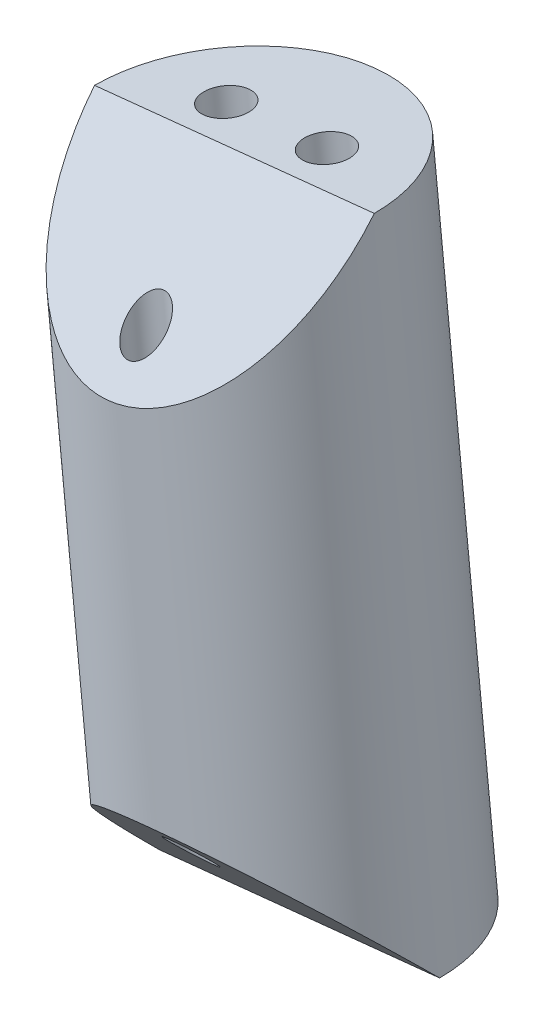
SolidWorks part; units mm, degrees
ref_plane "Front Plane" through (0, 0, 0) normal (0, 0, 1) x (1, 0, 0)
ref_plane "Top Plane" through (0, 0, 0) normal (0, 1, 0) x (1, 0, 0)
ref_plane "Right Plane" through (0, 0, 0) normal (1, 0, 0) x (0, 0, -1)
sketch "Sketch2" plane through (0, 0, 0) normal (0, 0, 1) x (1, 0, 0)
  line L0 (0, 0) -> (90, 0)
  line L1 (90, 0) -> (90, 120)
  line L2 (90, 120) -> (0, 120)
  line L3 (0, 120) -> (0, 0)
  line L4 (0, 120) -> (-10, 120)
  line L5 (-10, 120) -> (-10, 16.9491)
  line L6 (-10, 120) -> (57.5, 127)
  line L7 (57.5, 127) -> (90, 124)
  line L8 (90, 120) -> (99, 60)
  line L10 (90, 124) -> (90, 120)
  line L11 (5.9147, 0) -> (5.9147, -25)
  line L12 (5.9147, -25) -> (-4.0853, -25)
  line L13 (-4.0853, -29) -> (-4.0853, 0)
  line L14 (80, 0) -> (80, -25)
  line L15 (80, -25) -> (90, -25)
  line L16 (90, -29) -> (90, 0)
  line L17 (15.7927, 122.6748) -> (5.4776, 222.1414)
  line L18 (5.4776, 222.1414) -> (21.3923, 223.7918)
  line L19 (21.3923, 223.7918) -> (31.7073, 124.3252)
  line L20 (7.6492, 201.201) -> (23.5639, 202.8514)
  line L21 (10.9066, 169.7905) -> (26.8212, 171.441)
  line L22 (-10, 120) -> (-20.0396, 216.8108)
  line L23 (-20.0396, 216.8108) -> (-4.125, 218.4612)
  line L24 (-4.125, 218.4612) -> (5.9147, 121.6504)
  line L25 (-17.926, 196.4296) -> (-2.0114, 198.08)
  line L26 (-14.7556, 165.8578) -> (1.159, 167.5082)
  line L27 (57.5, 127) -> (46.9095, 229.1223)
  line L28 (46.9095, 229.1223) -> (30.9949, 227.4719)
  line L29 (30.9949, 227.4719) -> (41.5853, 125.3496)
  line L30 (33.2245, 205.9725) -> (49.1391, 207.6229)
  line L31 (36.5688, 173.7233) -> (52.4835, 175.3737)
  line L34 (90, 124) -> (99.1917, 223.5767)
  line L35 (99.1917, 223.5767) -> (83.2594, 225.0473)
  line L36 (83.2594, 225.0473) -> (74.0677, 125.4707)
  line L38 (81.3243, 204.0838) -> (97.2566, 202.6132)
  line L39 (78.4217, 172.6386) -> (94.354, 171.1679)
  line L40 (62.4078, 79.6749) -> (57.5, 127) construction
  line L41 (41.5853, 125.3496) -> (46.4931, 78.0244) construction
  line L42 (46.4931, 78.0244) -> (62.4078, 79.6749) construction
  line L43 (31.7073, 124.3252) -> (36.6151, 77.0001) construction
  line L44 (36.6151, 77.0001) -> (20.7005, 75.3496) construction
  line L45 (20.7005, 75.3496) -> (15.7927, 122.6748) construction
  line L46 (5.9147, 121.6504) -> (10.8224, 74.3253) construction
  line L47 (10.8224, 74.3253) -> (-5.0922, 72.6749) construction
  line L48 (-5.0922, 72.6749) -> (-10, 120) construction
  line L49 (74.0677, 125.4707) -> (69.6944, 78.0931) construction
  line L50 (69.6944, 78.0931) -> (85.7624, 78.0931) construction
  line L51 (85.7624, 78.0931) -> (90, 124) construction
  line L52 (-12.0823, 217.636) -> (10.4873, 0) construction
  line L53 (13.4349, 222.9666) -> (36.5574, 0) construction
  line L54 (38.9522, 228.2971) -> (62.6275, 0) construction
  line L55 (91.2256, 224.312) -> (70.5198, 0) construction
  line L59 (99, 60) -> (93.5277, 44.9649)
  line L60 (99, 60) -> (169.4769, 34.3485)
  line L61 (169.4769, 34.3485) -> (164.0046, 19.3134)
  line L62 (164.0046, 19.3134) -> (93.5277, 44.9649)
  line L63 (90, -2) -> (100, -2)
  line L64 (141.2862, 44.6091) -> (135.8138, 29.574)
  line L65 (99, 60) -> (55.7741, 75.7329) construction
  line L66 (55.7741, 75.7329) -> (50.3018, 60.6978) construction
  line L67 (100, -2) -> (100, -29)
  line L70 (-4.0853, -2) -> (-14.0853, -2)
  line L71 (-14.0853, -2) -> (-14.0853, -29)
  line L74 (-4.0853, 0) -> (0, 0)
  line L75 (-14.0853, -29) -> (-14.0853, -112.587)
  line L76 (-14.0853, -112.587) -> (100, -112.587)
  line L77 (100, -112.587) -> (100, -29)
  line L78 (-14.0853, -29) -> (100, -29)
  line L79 (-14.0853, -14.5) -> (100, -14.5) construction
  line L80 (31.7073, -112.587) -> (31.7073, -122.6232)
  line L81 (31.7073, -122.6232) -> (42.9573, -122.6232)
  line L82 (42.9573, -122.6232) -> (42.9573, -112.587)
  line L83 (-14.0853, -112.587) -> (-88.3667, -112.587)
  line L84 (-88.3667, -112.587) -> (-88.3667, -128.2699)
  line L85 (-88.3667, -128.2699) -> (169.4958, -128.2699)
  line L86 (169.4958, -128.2699) -> (169.4958, -112.587)
  line L87 (169.4958, -112.587) -> (100, -112.587)
  line L88 (90, 60) -> (-10, 60) construction
  line L89 (50.3018, 60.6978) -> (93.5277, 44.9649) construction
  line L90 (87.2806, 55.7521) -> (166.7408, 26.8309) construction
  line L91 (87.2806, 55.7521) -> (82.1749, 52.5336) construction
  line L92 (82.1749, 52.5336) -> (77.3257, 0) construction
  line L93 (83.1185, 56.6957) -> (86.337, 51.59) construction
  arc A0 (-10, 16.9491) -> (-4.0853, 0) centre (14.9876, 16.1624) ccw
  arc A1 (93.5277, 44.9649) -> (90, 0) centre (-126.4069, 39.5988) cw
  point P42 (41.1818, 206.7977)
  point P100 (84.7278, 54.1428)
  point P101 (84.7278, 54.1428)
  dimension "D11" = 47.3684
  dimension "D35" = 9
  dimension "D32" = 220
  dimension "D36" = 25
  dimension "D1" = 120
  dimension "D2" = 90
  dimension "D3" = 10
  dimension "D5" = 67.862
  dimension "D6" = 7
  dimension "D7" = 4
  dimension "D8" = 16
  dimension "D9" = 16
  dimension "D10" = 100
  dimension "D12" = 31.5789
  dimension "D13" = 16
  dimension "D14" = 16
  dimension "D15" = 16
  dimension "D16" = 25.7927
  dimension "D17" = 100
  dimension "D18" = 21.0526
  dimension "D19" = 31.5789
  dimension "D20" = 97.33
  dimension "D21" = 102.67
  dimension "D22" = 20.4905
  dimension "D23" = 30.7358
  dimension "D24" = 21.6147
  dimension "D25" = 32.4221
  dimension "D26" = 25
  dimension "D28" = 25
  dimension "D29" = 75
  dimension "D30" = 47.5789
  dimension "D31" = 30
  dimension "D33" = 46
  dimension "D34" = 20
  dimension "D37" = 2
  dimension "D38" = 2
  dimension "D39" = 27
  dimension "D40" = 10
  dimension "D41" = 10
  dimension "D42" = 27
  dimension "D43" = 14.5
  dimension "D44" = 127.5
ref_plane "Plane1" through (87.2806, 55.7521, 0) normal (-0.846, -0.5333, 0) x (0, 0, 1)
ref_plane "Plane2" through (82.1749, 52.5336, 0) normal (-0.0919, -0.9958, 0) x (-0.9958, 0.0919, 0)
ref_plane "Plane3" through (91.2256, 224.312, 0) normal (-0.0919, -0.9958, 0) x (-0.9958, 0.0919, 0)
ref_plane "Plane4" through (38.9522, 228.2971, 0) normal (0.1032, -0.9947, 0) x (-0.9947, -0.1032, 0)
ref_plane "Plane5" through (13.4349, 222.9666, 0) normal (0.1032, -0.9947, 0) x (-0.9947, -0.1032, 0)
ref_plane "Plane7" through (166.7408, 26.8309, 0) normal (0.9397, -0.342, 0) x (0, 0, -1)
ref_plane "Plane8" through (110.4217, -40.1902, 0) normal (0.9397, -0.342, 0) x (0, 0, -1)
ref_plane "Plane9" through (19.3664, 209.803, 0) normal (-0.0919, -0.9958, 0) x (-0.9958, 0.0919, 0)
ref_plane "Plane10" through (16.4638, 178.3578, 0) normal (-0.0919, -0.9958, 0) x (-0.9958, 0.0919, 0)
ref_plane "Plane11" through (-20.7793, 200.3721, 0) normal (0.1032, -0.9947, 0) x (-0.9947, -0.1032, 0)
ref_plane "Plane12" through (-17.435, 168.1229, 0) normal (0.1032, -0.9947, 0) x (-0.9947, -0.1032, 0)
ref_plane "Plane13" through (-20.5619, 198.2754, 0) normal (0.1032, -0.9947, 0) x (-0.9947, -0.1032, 0)
ref_plane "Plane14" through (-17.3045, 166.8649, 0) normal (0.1032, -0.9947, 0) x (-0.9947, -0.1032, 0)
ref_plane "Plane15" through (-12.0823, 217.636, 0) normal (0.1032, -0.9947, 0) x (-0.9947, -0.1032, 0)
ref_plane "Plane16" through (-20.3445, 196.1788, 0) normal (0.1032, -0.9947, 0) x (-0.9947, -0.1032, 0)
ref_plane "Plane17" through (-17.1741, 165.607, 0) normal (0.1032, -0.9947, 0) x (-0.9947, -0.1032, 0)
ref_plane "Plane18" through (12.1098, 131.1899, 0) normal (-0.0919, -0.9958, 0) x (-0.9958, 0.0919, 0)
ref_plane "Plane19" through (-12.4184, 119.7492, 0) normal (0.1032, -0.9947, 0) x (-0.9947, -0.1032, 0)
ref_plane "Plane20" through (0, 0, 0) normal (0, 0, 1) x (0.1032, -0.9947, 0)
ref_plane "Plane21" through (0, 0, 0) normal (0, 0, 1) x (-0.0919, -0.9958, 0)
ref_plane "Plane22" through (10.3758, 1.076, 0) normal (-0.9947, -0.1032, 0) x (0.1032, -0.9947, 0)
ref_plane "Plane23" through (36.1684, 3.7508, 0) normal (-0.9947, -0.1032, 0) x (0.1032, -0.9947, 0)
ref_plane "Plane24" through (61.9611, 6.4256, 0) normal (-0.9947, -0.1032, 0) x (0.1032, -0.9947, 0)
ref_plane "Plane25" through (69.924, -6.4545, 0) normal (-0.9958, 0.0919, 0) x (-0.0919, -0.9958, 0)
sketch "Sketch3" plane through (-20.3445, 196.1788, 0) normal (0.1032, -0.9947, 0) x (-0.9947, -0.1032, 0)
  line L0 (-2.4314, 0) -> (-18.4314, 0) construction
  circle A0 centre (-10.4314, 0) radius 10
  dimension "D1" = 20
extrude "Boss-Extrude1" add sketch "Sketch3" along normal blind 45
sketch "Sketch4" plane through (10.3758, 1.076, 0) normal (-0.9947, -0.1032, 0) x (0.1032, -0.9947, 0)
  line L0 (-197.2309, 0) -> (-187.2309, 10)
  line L1 (-197.2309, 10) -> (-197.2309, -10) construction
  line L2 (-152.2309, 10) -> (-197.2309, 10) construction
  line L3 (-187.2309, 10) -> (-197.2309, 10)
  line L4 (-197.2309, 10) -> (-197.2309, 0)
  line L5 (-162.2309, 10) -> (-152.2309, 10)
  line L6 (-152.2309, 10) -> (-152.2309, 0)
  line L7 (-217.7214, 0) -> (1.0818, 0) construction
  line L8 (-152.2309, 0) -> (-162.2309, 10)
  dimension "D1" = 45
  dimension "D2" = 45
extrude "Cut-Extrude1" cut sketch "Sketch4" against normal through all and the other way through all
sketch "Sketch5" plane through (10.3758, 1.076, 0) normal (-0.9947, -0.1032, 0) x (0.1032, -0.9947, 0)
  line L0 (-152.2309, 0) -> (-156.2309, 4)
  line L1 (-152.2309, 0) -> (-162.2309, 10) construction
  line L2 (-156.2309, 4) -> (-148.2309, 4)
  line L3 (-148.2309, 4) -> (-148.2309, 0)
  line L4 (-213.7055, 0) -> (7.2742, 0) construction
  line L6 (-152.2309, 0) -> (-148.2309, 4) construction
  line L7 (-148.2309, 0) -> (-152.2309, -4)
  line L8 (-152.2309, -10) -> (-152.2309, 0) construction
  line L9 (-152.2309, -4) -> (-152.2309, 0)
  dimension "D1" = 4
  dimension "D2" = 45
sketch "Sketch7" plane through (10.3758, 1.076, 0) normal (-0.9947, -0.1032, 0) x (0.1032, -0.9947, 0)
  line L0 (-193.2309, 4) -> (-197.2309, 0)
  line L1 (-217.7214, 0) -> (1.0818, 0) construction
  line L4 (-197.2309, -4) -> (-197.2309, 0)
  line L5 (-193.2309, 4) -> (-193.2309, 0)
  arc A0 (-197.2309, -4) -> (-193.2309, 0) centre (-197.2309, 0) ccw
  dimension "D1" = 4
  dimension "D2" = 4
sketch "Sketch8" plane through (-20.3445, 196.1788, 0) normal (-0.1032, 0.9947, 0) x (0.9947, 0.1032, 0)
  line L0 (2.4314, 0) -> (18.4314, 0) construction
  circle A0 centre (6.8314, 3) radius 1.6
  circle A1 centre (14.0314, 3) radius 1.6
  circle A2 centre (10.4314, -7) radius 1.4
  point P9 (10.4314, 0)
  dimension "D1" = 3.2
  dimension "D2" = 3.2
  dimension "D3" = 2.8
  dimension "D4" = 3
  dimension "D5" = 3
  dimension "D6" = 3.6
  dimension "D7" = 3.6
  dimension "D8" = 7
extrude "Cut-Extrude3" cut sketch "Sketch8" against normal through all and the other way through all
sketch "Sketch9" plane through (-15.7027, 151.4188, 0) normal (0.1032, -0.9947, 0) x (0.9947, 0.1032, 0)
  line L0 (2.4314, -6) -> (18.4314, -6)
  line L2 (2.4314, 0) -> (18.4314, 0) construction
  arc A0 (0.4314, 0) -> (20.4314, 0) centre (10.4314, 0) ccw construction
  arc A1 (2.4314, -6) -> (18.4314, -6) centre (10.4314, 0) ccw
  dimension "D1" = 6
